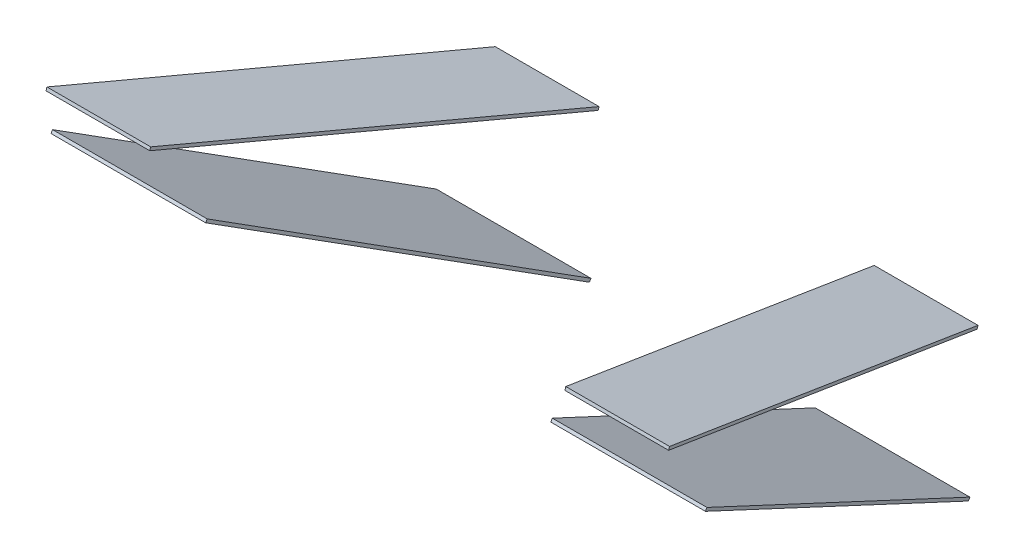
SolidWorks part; units mm, degrees
ref_plane "Front Plane" through (0, 0, 0) normal (0, 0, 1) x (1, 0, 0)
ref_plane "Top Plane" through (0, 0, 0) normal (0, 1, 0) x (1, 0, 0)
ref_plane "Right Plane" through (0, 0, 0) normal (1, 0, 0) x (0, 0, -1)
ref_plane "Plane1" through (0, 329.6996, -103.9539) normal (0, 0.9537, -0.3007) x (1, 0, 0)
sketch "Sketch1" plane through (0, 329.6996, -103.9539) normal (0, 0.9537, -0.3007) x (1, 0, 0)
  line L0 (102, 27.2172) -> (153, 27.2172)
  line L1 (102, 27.2172) -> (67.6162, 222.2172)
  line L2 (153, 27.2172) -> (118.6162, 222.2172)
  line L3 (67.6162, 222.2172) -> (118.6162, 222.2172)
  line L4 (0, 0) -> (0, 229.5182) construction
  dimension "D1" = 51
  dimension "D2" = 195
  dimension "D3" = 10
  dimension "D4" = 102
extrude "Boss-Extrude1" add sketch "Sketch1" along normal blind 1.5
ref_plane "Plane2" through (0, 283.0225, -160.1264) normal (0, -0.8704, 0.4924) x (1, 0, 0)
sketch "Sketch2" plane through (0, 283.0225, -160.1264) normal (0, -0.8704, 0.4924) x (1, 0, 0)
  line L0 (84.8101, 22.9105) -> (160.8101, 22.9105)
  line L1 (0, 0) -> (0, -224.1327) construction
  line L2 (84.8101, 22.9105) -> (55.12, -159.6916)
  line L3 (55.12, -159.6916) -> (131.12, -159.6916)
  line L4 (131.12, -159.6916) -> (160.8101, 22.9105)
  line L5 (118.6162, -145.1743) -> (67.6162, -145.1743) construction
  point P4 (93.1162, -145.1743)
  point P11 (93.12, -159.6916)
  dimension "D1" = 76
  dimension "D2" = 185
  dimension "D3" = 93.12
  dimension "D4" = 93.1162
  dimension "D5" = 84.8101
extrude "Boss-Extrude2" add sketch "Sketch2" against normal blind 1.5 separate body
mirror "Mirror2" about plane through (0, 0, 0) normal (1, 0, 0) of bodies 101 103
ref_plane "Plane3" through (0, 0, 330) normal (0, 0, 1) x (1, 0, 0)
sketch "Sketch3" plane through (0, 0, 330) normal (0, 0, 1) x (1, 0, 0)
  ellipse E0 centre (-76.608, -47.5751) end of major axis (-77.5766, 48.7541) minor radius 85.8756
  ellipse E1 centre (-76.608, -47.5751) end of major axis (-75.6394, -143.9044) minor radius 85.8756 construction
  ellipse E2 centre (73.0541, -47.7981) end of major axis (80.538, -143.7932) minor radius 85.8781
  ellipse E3 centre (73.0541, -47.7981) end of major axis (80.538, -143.7932) minor radius 85.8781 construction
  point P22 (-1.4258, -94.3261)
